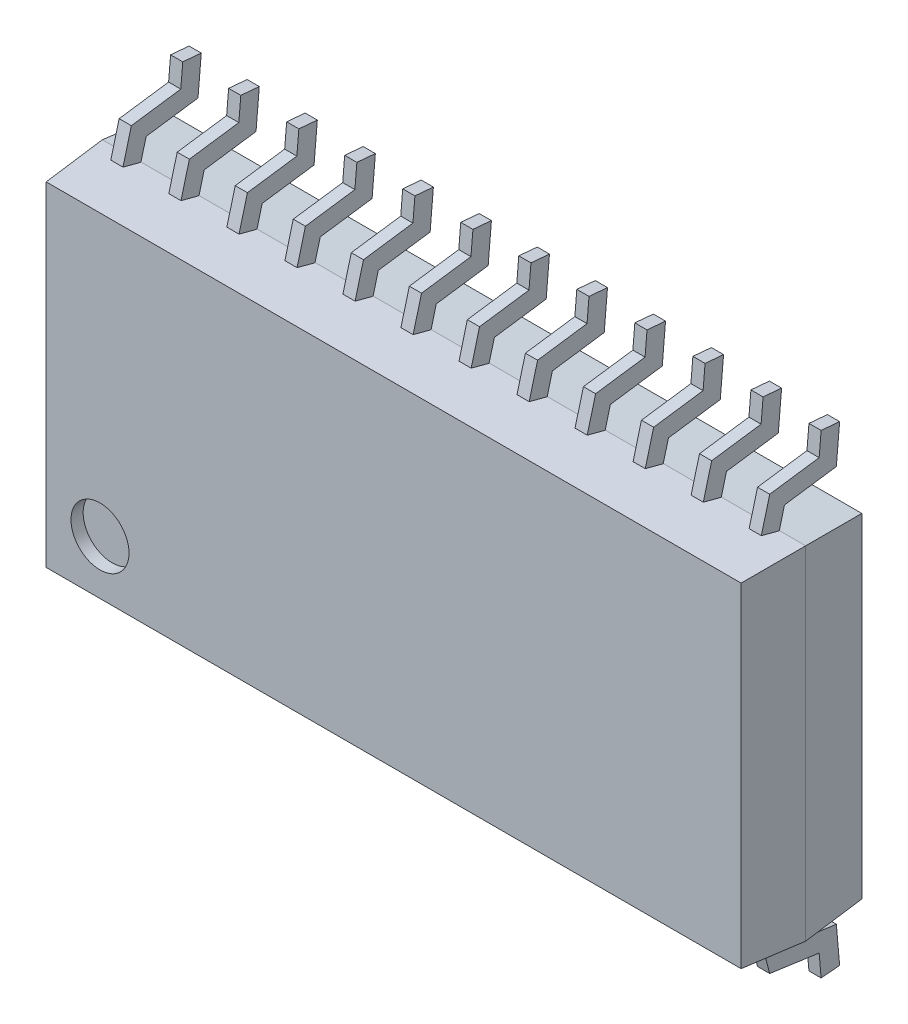
SolidWorks part; units mm, degrees
ref_plane "Front Plane" through (0, 0, 0) normal (0, 0, 1) x (1, 0, 0)
ref_plane "Top Plane" through (0, 0, 0) normal (0, 1, 0) x (1, 0, 0)
ref_plane "Right Plane" through (0, 0, 0) normal (1, 0, 0) x (0, 0, -1)
sketch "Sketch1" plane through (0, 0, 0) normal (0, 0, 1) x (1, 0, 0)
  line L1 (0, 0) -> (15.3924, 0)
  line L2 (0, 0) -> (0, 7.493)
  line L3 (0, 7.493) -> (15.3924, 7.493)
  line L4 (15.3924, 0) -> (15.3924, 7.493)
  dimension "D1" = 7.493
  dimension "D2" = 15.3924
extrude "Boss-Extrude1" add sketch "Sketch1" along normal blind 1.3208 draft 4
mirror "Mirror1" about plane through (0, 0, 0) normal (0, 0, 1) of "Boss-Extrude1"
ref_plane "Plane1" through (0.7112, 0, 0) normal (-1, 0, 0) x (0, 0, 1)
sketch "Sketch3" plane through (0.7112, 0, 0) normal (-1, 0, 0) x (0, 0, 1)
  line L4 (-1.2492, -0.5931) -> (-1.3208, -1.4097)
  line L5 (-0.1146, -0.4332) -> (-1.2492, -0.5931)
  line L6 (0, 0) -> (-0.1146, -0.4332)
extrude "Extrude-Thin4" add sketch "Sketch3" along normal mid plane 0.2667 separate body thin thin type one direction reverse wall 0.4064
pattern_linear "LPattern1" count 12 spacing 1.27 along (1, 0, 0) of "Extrude-Thin4"
ref_plane "Plane2" through (0, 3.744, 0) normal (0, 1, 0) x (1, 0, 0)
mirror "Mirror2" about plane through (0, 3.744, 0) normal (0, 1, 0) of "Extrude-Thin4", "LPattern1"
sketch "Sketch5" plane through (0, 0, 1.3208) normal (0, 0, 1) x (1, 0, 0)
  circle A0 centre (1.27, 1.27) radius 0.635
extrude "Cut-Extrude1" cut sketch "Sketch5" against normal blind 0.2667
